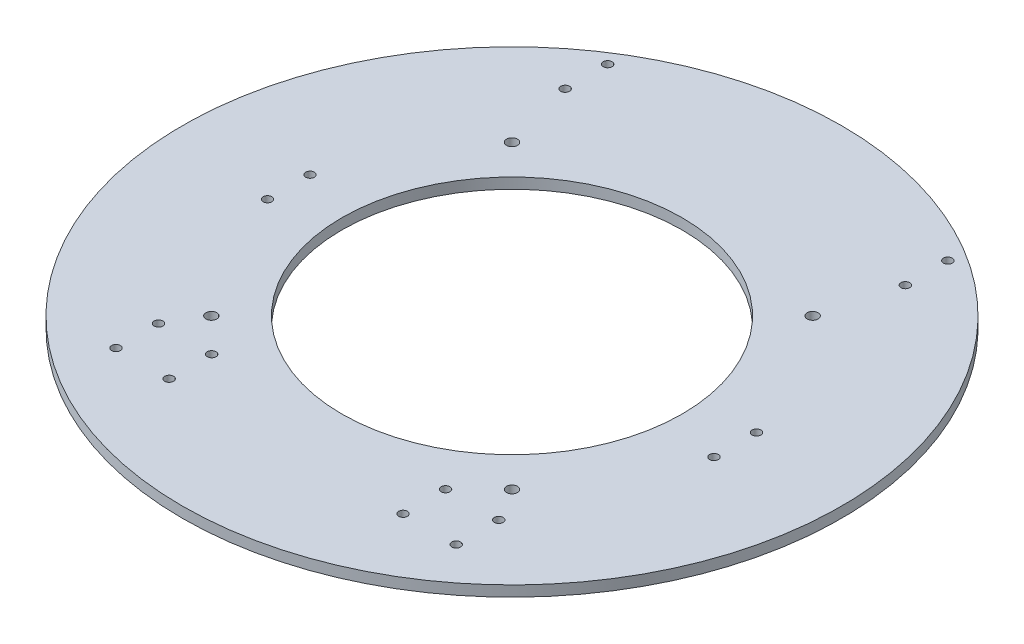
SolidWorks part; units mm, degrees
material "PC High Viscosity"
ref_plane "Front Plane" through (0, 0, 0) normal (0, 0, 1) x (1, 0, 0)
ref_plane "Top Plane" through (0, 0, 0) normal (0, 1, 0) x (1, 0, 0)
ref_plane "Right Plane" through (0, 0, 0) normal (1, 0, 0) x (0, 0, -1)
sketch "Sketch1" plane through (0, 0, 0) normal (0, 1, 0) x (1, 0, 0)
  line L0 (0, 0) -> (0, -95.25) construction
  line L1 (0, -95.25) -> (82.55, -95.25) construction
  line L2 (82.55, -95.25) -> (82.55, -146.0008) construction
  line L3 (82.55, -95.25) -> (88.9, -95.25) construction
  line L4 (88.9, -95.25) -> (88.9, -146.0008) construction
  line L5 (69.85, -109.5375) -> (69.85, -134.9375) construction
  line L6 (101.6, -109.5375) -> (101.6, -134.9375) construction
  line L7 (69.85, -109.5375) -> (101.6, -109.5375) construction
  line L8 (0, 0) -> (89.8026, -89.8026) construction
  line L9 (0, 0) -> (0, 133.35) construction
  line L10 (0, 133.35) -> (101.6, 133.35) construction
  line L11 (101.6, 133.35) -> (101.6, 158.75) construction
  line L12 (0, 0) -> (89.8026, 89.8026) construction
  line L13 (0, 0) -> (133.35, 0) construction
  line L14 (133.35, 0) -> (133.35, -12.7) construction
  line L15 (133.35, 0) -> (133.35, 12.7) construction
  line L16 (101.6, -134.9375) -> (118.4058, -157.2577) construction
  line L17 (101.6, -134.9375) -> (0, 0) construction
  circle A0 centre (0, 0) radius 101.6
  circle A1 centre (69.85, -109.5375) radius 2.6289
  circle A2 centre (69.85, -134.9375) radius 2.6289
  circle A3 centre (101.6, -109.5375) radius 2.6289
  circle A4 centre (101.6, -134.9375) radius 2.6289
  circle A5 centre (89.8026, -89.8026) radius 3.2639
  circle A6 centre (101.6, 133.35) radius 2.6289
  circle A7 centre (101.6, 158.75) radius 2.6289
  circle A10 centre (89.8026, 89.8026) radius 3.2639
  circle A11 centre (133.35, -12.7) radius 2.6289
  circle A12 centre (133.35, 12.7) radius 2.6289
  circle A13 centre (0, 0) radius 196.85
  circle A14 centre (-69.85, -134.9375) radius 2.6289
  circle A15 centre (-101.6, -134.9375) radius 2.6289
  circle A16 centre (-101.6, -109.5375) radius 2.6289
  circle A17 centre (-89.8026, -89.8026) radius 3.2639
  circle A18 centre (-69.85, -109.5375) radius 2.6289
  circle A19 centre (-133.35, -12.7) radius 2.6289
  circle A20 centre (-133.35, 12.7) radius 2.6289
  circle A21 centre (-89.8026, 89.8026) radius 3.2639
  circle A22 centre (-101.6, 158.75) radius 2.6289
  circle A23 centre (-101.6, 133.35) radius 2.6289
  point P52 (101.6, 153.6437)
  point P53 (101.6, 117.812)
  point P54 (101.6, 140.7635)
  dimension "D1" = 82.55
  dimension "D4" = 12.7
  dimension "D5" = 5.2578
  dimension "D7" = 5.2578
  dimension "D8" = 25.4
  dimension "D9" = 5.2578
  dimension "D10" = 5.2578
  dimension "D15" = 6.5278
  dimension "D18" = 5.2578
  dimension "D20" = 5.2578
  dimension "D21" = 127
  dimension "D22" = 6.5278
  dimension "D25" = 5.2578
  dimension "D26" = 5.2578
  dimension "D28" = 393.7
  dimension "D29" = 203.2
  dimension "D19" = 25.4
  dimension "D2" = 95.25
  dimension "D3" = 6.35
  dimension "D6" = 25.4
  dimension "D11" = 14.2875
  dimension "D12" = 12.7
  dimension "D13" = 127
  dimension "D14" = 45
  dimension "D16" = 101.6
  dimension "D17" = 228.6
  dimension "D23" = 12.7
  dimension "D24" = 12.7
  dimension "D27" = 133.35
extrude "Boss-Extrude1" add sketch "Sketch1" along normal blind 6.35
ref_plane "Plane1" through (0, 0, 0) normal (1, 0, 0) x (0, 0, -1)
